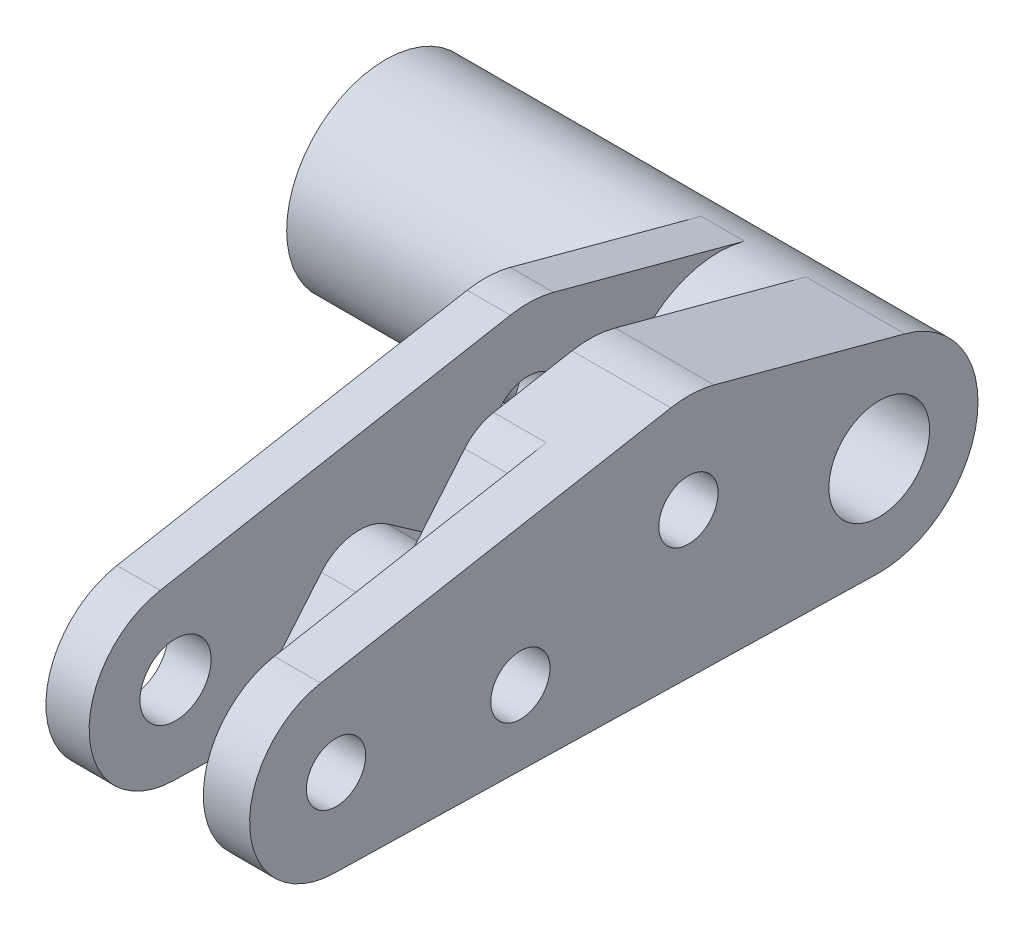
SolidWorks part; units mm, degrees
ref_plane "Front Plane" through (0, 0, 0) normal (0, 0, 1) x (1, 0, 0)
ref_plane "Top Plane" through (0, 0, 0) normal (0, 1, 0) x (1, 0, 0)
ref_plane "Right Plane" through (0, 0, 0) normal (1, 0, 0) x (0, 0, -1)
sketch "Sketch1" plane through (0, 0, 0) normal (1, 0, 0) x (0, 0, -1)
  line L0 (-0.1443, -6.3484) -> (-35.0513, -5.5548)
  line L1 (-35.9129, 5.4677) -> (-13.3962, 9.5358)
  line L2 (-10.6238, 9.4206) -> (1.6435, 6.1336)
  line L3 (-34.925, 0) -> (0, 0) construction
  line L4 (0, 0) -> (-12.2673, 3.287) construction
  arc A0 (-0.1443, -6.3484) -> (1.6435, 6.1336) centre (0, 0) ccw
  arc A1 (-35.0513, -5.5548) -> (-35.9129, 5.4677) centre (-34.925, 0) cw
  arc A2 (-13.3962, 9.5358) -> (-10.6238, 9.4206) centre (-12.2673, 3.287) cw
  dimension "D1" = 6.35
  dimension "D2" = 11.1125
  dimension "D3" = 34.925
  dimension "D4" = 12.7
  dimension "D5" = 15
extrude "Boss-Extrude1" add sketch "Sketch1" against normal blind 13.0969
sketch "Sketch6" plane through (0, 0, 0) normal (1, 0, 0) x (0, 0, -1)
  line L0 (1.6435, 6.1336) -> (-10.6238, 9.4206) construction
  line L1 (-13.3962, 9.5358) -> (-35.9129, 5.4677) construction
  line L2 (1.6435, 6.1336) -> (-10.6238, 9.4206)
  line L3 (-13.3962, 9.5358) -> (-35.9129, 5.4677)
  line L5 (-23.6779, 3.5249) -> (-30.0606, -4.0817)
  line L6 (-35.0513, -5.5548) -> (-0.1443, -6.3484) construction
  line L7 (-35.0513, -5.5548) -> (-31.9779, -5.6247)
  line L8 (-34.925, 0) -> (0, 0) construction
  line L9 (-15.9095, -1.9146) -> (-23.6779, 3.5249)
  arc A0 (-10.6238, 9.4206) -> (-13.3962, 9.5358) centre (-12.2673, 3.287) ccw construction
  arc A1 (-35.9129, 5.4677) -> (-35.0513, -5.5548) centre (-34.925, 0) ccw construction
  arc A2 (-10.6238, 9.4206) -> (-13.3962, 9.5358) centre (-12.2673, 3.287) ccw
  arc A3 (-35.9129, 5.4677) -> (-35.0513, -5.5548) centre (-34.925, 0) ccw
  arc A4 (1.6435, 6.1336) -> (-6.1336, 1.6435) centre (0, 0) ccw
  arc A5 (-6.1336, 1.6435) -> (-15.9095, -1.9146) centre (-12.2673, 3.287) cw
  arc A6 (-30.0606, -4.0817) -> (-31.9779, -5.6247) centre (-34.925, 0) cw
  dimension "D1" = 6.35
  dimension "D2" = 50
  dimension "D3" = 35
extrude "Cut-Extrude4" cut sketch "Sketch6" against normal blind 3.9688 from offset 6.35 offset against normal yes
ref_plane "Plane1" through (-6.5484, 0, 0) normal (1, 0, 0) x (0, 0, -1)
sketch "Sketch7" plane through (-6.5484, 0, 0) normal (1, 0, 0) x (0, 0, -1)
  line L0 (-30.0606, -4.0817) -> (-23.6779, 3.5249) construction
  line L2 (-13.3962, 9.5358) -> (-35.9129, 5.4677) construction
  line L3 (-30.0606, -4.0817) -> (-19.5701, 8.4204)
  line L4 (-35.0513, -5.5548) -> (-0.1443, -6.3484) construction
  line L5 (-19.5701, 8.4204) -> (-35.9129, 5.4677)
  line L6 (-35.0513, -5.5548) -> (-31.9779, -5.6247)
  arc A0 (-31.9779, -5.6247) -> (-30.0606, -4.0817) centre (-34.925, 0) ccw construction
  arc A1 (-35.9129, 5.4677) -> (-35.0513, -5.5548) centre (-34.925, 0) ccw construction
  arc A2 (-31.9779, -5.6247) -> (-30.0606, -4.0817) centre (-34.925, 0) ccw
  arc A3 (-35.9129, 5.4677) -> (-35.0513, -5.5548) centre (-34.925, 0) ccw
extrude "Cut-Extrude6" cut sketch "Sketch7" against normal mid plane 7.1437
sketch "Sketch3" plane through (0, 0, 0) normal (1, 0, 0) x (0, 0, -1)
  line L0 (-35.0513, -5.5548) -> (-0.1443, -6.3484) construction
  line L1 (-23.0739, -1.0634) -> (-21.1168, 1.7316) construction
  line L2 (-23.0739, -1.0634) -> (-25.6876, 1.1298) construction
  line L3 (-23.6779, 3.5249) -> (-15.9095, -1.9146) construction
  line L4 (-30.0606, -4.0817) -> (-23.6779, 3.5249) construction
  circle A0 centre (0, 0) radius 3.2385
  circle A1 centre (-34.925, 0) radius 1.905
  circle A2 centre (-12.2673, 3.287) radius 1.905
  circle A3 centre (-23.0739, -1.0634) radius 1.905
  circle A4 centre (-23.0739, -1.0634) radius 4.7625 construction
  circle A5 centre (-34.925, 0) radius 4.7625 construction
  dimension "D1" = 3.81
  dimension "D2" = 6.477
  dimension "D3" = 9.525
extrude "Cut-Extrude2" cut sketch "Sketch3" against normal through all
sketch "Sketch4" plane through (-13.0969, 0, 0) normal (-1, 0, 0) x (0, 0, 1)
  circle A0 centre (0, 0) radius 6.35
  circle A1 centre (0, 0) radius 3.2385
  circle A2 centre (0, 0) radius 3.2385 construction
  arc A3 (-1.6435, 6.1336) -> (0.1443, -6.3484) centre (0, 0) ccw construction
extrude "Boss-Extrude2" add sketch "Sketch4" along normal up to surface (18.6531 mm away)
sketch "Sketch5" plane through (-13.0969, 0, 0) normal (-1, 0, 0) x (0, 0, 1)
  circle A0 centre (12.2673, 3.287) radius 2.286
  circle A1 centre (23.0739, -1.0634) radius 2.286
  circle A2 centre (34.925, 0) radius 2.286
  dimension "D1" = 4.572
extrude "Cut-Extrude5" cut sketch "Sketch5" against normal up to surface (2.7781 mm away) up to face at (-10.3187, 3.287, 10.3623)
fillet "Fillet1" radius 3.175 2 edges at (-8.3344, 3.5249, 23.6779) (-4.6633, 8.4204, 19.5701)
